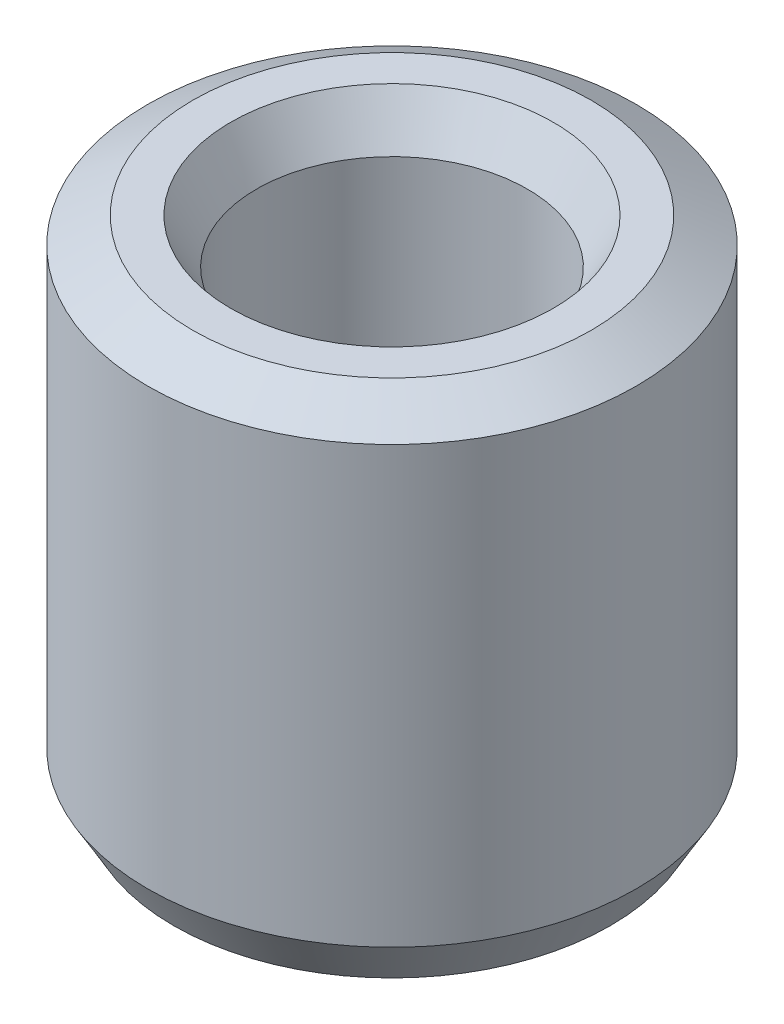
SolidWorks part; units mm, degrees
ref_plane "Front Plane" through (0, 0, 0) normal (0, 0, 1) x (1, 0, 0)
ref_plane "Top Plane" through (0, 0, 0) normal (0, 1, 0) x (1, 0, 0)
ref_plane "Right Plane" through (0, 0, 0) normal (1, 0, 0) x (0, 0, -1)
sketch "Sketch1" plane through (0, 0, 0) normal (0, 1, 0) x (1, 0, 0)
  circle A0 centre (0, 0) radius 37.5
  dimension "SLEEVE_OD" = 75
extrude "Boss-Extrude1" add sketch "Sketch1" along normal blind 77.7494
sketch "Sketch2" plane through (0, 0, 0) normal (0, 1, 0) x (1, 0, 0)
  circle A0 centre (0, 0) radius 20.79
  dimension "BORE_D" = 41.5801
extrude "Cut-Extrude1" cut sketch "Sketch2" along normal through all
chamfer "Chamfer1" distance 3.9814 angle 60 4 edges at (0, 77.7494, 20.79) (0, 0, 20.79) (0, 0, 37.5) (0, 77.7494, 37.5) first distance on face at (0, 77.7494, 20.79) first distance on face at (0, 0, 20.79) first distance on face at (0, 77.7494, 37.5)
